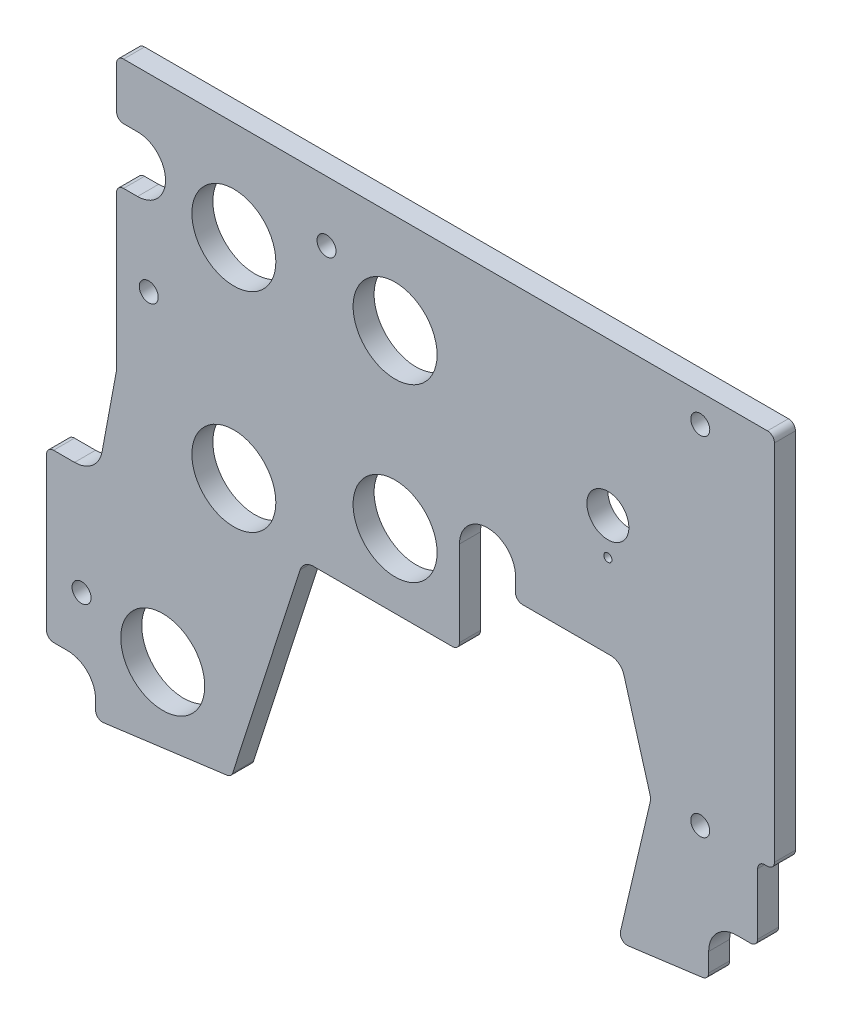
SolidWorks part; units mm, degrees
ref_plane "Front Plane" through (0, 0, 0) normal (0, 0, 1) x (1, 0, 0)
ref_plane "Top Plane" through (0, 0, 0) normal (0, 1, 0) x (1, 0, 0)
ref_plane "Right Plane" through (0, 0, 0) normal (1, 0, 0) x (0, 0, -1)
sketch "Sketch1" plane through (0, 0, 0) normal (0, 0, 1) x (1, 0, 0)
  line L24 (-1.5875, -85.5345) -> (-1.5875, -3.175)
  line L25 (-3.175, -1.5875) -> (-149.225, -1.5875)
  line L26 (-150.8125, -3.175) -> (-150.8125, -12.7)
  line L27 (-149.225, -14.2875) -> (-146.05, -14.2875)
  line L28 (-146.05, -26.9875) -> (-149.225, -26.9875)
  line L29 (-150.8125, -28.575) -> (-150.8125, -63.3539)
  line L30 (-150.8392, -63.6437) -> (-154.0942, -81.1696)
  line L31 (-160.3375, -86.36) -> (-165.1, -86.36)
  line L32 (-166.6875, -87.9475) -> (-166.6875, -122.5455)
  line L33 (-165.1, -124.133) -> (-161.925, -124.133)
  line L34 (-155.575, -130.483) -> (-155.575, -132.6404)
  line L35 (-153.7803, -134.2144) -> (-125.7711, -130.5269)
  line L36 (-124.467, -129.4389) -> (-109.1805, -81.8956)
  line L37 (-106.1579, -79.6925) -> (-74.6125, -79.6925)
  line L38 (-73.025, -78.105) -> (-73.025, -58.7375)
  line L39 (-60.325, -58.7375) -> (-60.325, -61.9125)
  line L40 (-58.7375, -63.5) -> (-38.7866, -63.5)
  line L41 (-35.7358, -65.7958) -> (-29.8313, -86.2841)
  line L42 (-29.7909, -87.8878) -> (-36.5223, -116.6102)
  line L43 (-34.7695, -118.5463) -> (-17.8903, -116.3241)
  line L44 (-16.51, -114.7502) -> (-16.51, -110.5169)
  line L45 (-10.16, -104.1528) -> (-6.985, -104.1528)
  line L46 (-5.3975, -102.5653) -> (-5.3975, -88.7095)
  line L47 (-3.81, -87.122) -> (-3.175, -87.122)
  line L48 (-1.5875, -85.5345) -> (-1.5875, -3.175)
  line L49 (-3.175, -1.5875) -> (-149.225, -1.5875)
  line L50 (-150.8125, -3.175) -> (-150.8125, -12.7)
  line L51 (-149.225, -14.2875) -> (-146.05, -14.2875)
  line L52 (-146.05, -26.9875) -> (-149.225, -26.9875)
  line L53 (-150.8125, -28.575) -> (-150.8125, -63.3539)
  line L54 (-150.8392, -63.6437) -> (-154.0942, -81.1696)
  line L55 (-160.3375, -86.36) -> (-165.1, -86.36)
  line L56 (-166.6875, -87.9475) -> (-166.6875, -122.5455)
  line L57 (-165.1, -124.133) -> (-161.925, -124.133)
  line L58 (-155.575, -130.483) -> (-155.575, -132.6404)
  line L59 (-153.7803, -134.2144) -> (-125.7711, -130.5269)
  line L60 (-124.467, -129.4389) -> (-109.1805, -81.8956)
  line L61 (-106.1579, -79.6925) -> (-74.6125, -79.6925)
  line L62 (-73.025, -78.105) -> (-73.025, -58.7375)
  line L63 (-60.325, -58.7375) -> (-60.325, -61.9125)
  line L64 (-58.7375, -63.5) -> (-38.7866, -63.5)
  line L65 (-35.7358, -65.7958) -> (-29.8313, -86.2841)
  line L66 (-29.7909, -87.8878) -> (-36.5223, -116.6102)
  line L67 (-34.7695, -118.5463) -> (-17.8903, -116.3241)
  line L68 (-16.51, -114.7502) -> (-16.51, -110.5169)
  line L69 (-10.16, -104.1528) -> (-6.985, -104.1528)
  line L70 (-5.3975, -102.5653) -> (-5.3975, -88.7095)
  line L71 (-3.81, -87.122) -> (-3.175, -87.122)
  arc A24 (-3.175, -87.122) -> (-1.5875, -85.5345) centre (-3.175, -85.5345) ccw
  arc A25 (-1.5875, -3.175) -> (-3.175, -1.5875) centre (-3.175, -3.175) ccw
  arc A26 (-149.225, -1.5875) -> (-150.8125, -3.175) centre (-149.225, -3.175) ccw
  arc A27 (-150.8125, -12.7) -> (-149.225, -14.2875) centre (-149.225, -12.7) ccw
  arc A28 (-146.05, -26.9875) -> (-146.05, -14.2875) centre (-146.05, -20.6375) ccw
  arc A29 (-149.225, -26.9875) -> (-150.8125, -28.575) centre (-149.225, -28.575) ccw
  arc A30 (-150.8392, -63.6437) -> (-150.8125, -63.3539) centre (-152.4, -63.3539) ccw
  arc A31 (-160.3375, -86.36) -> (-154.0942, -81.1696) centre (-160.3375, -80.01) ccw
  arc A32 (-165.1, -86.36) -> (-166.6875, -87.9475) centre (-165.1, -87.9475) ccw
  arc A33 (-166.6875, -122.5455) -> (-165.1, -124.133) centre (-165.1, -122.5455) ccw
  arc A34 (-155.575, -130.483) -> (-161.925, -124.133) centre (-161.925, -130.483) ccw
  arc A35 (-155.575, -132.6404) -> (-153.7803, -134.2144) centre (-153.9875, -132.6404) ccw
  arc A36 (-125.7711, -130.5269) -> (-124.467, -129.4389) centre (-125.9783, -128.953) ccw
  arc A37 (-106.1579, -79.6925) -> (-109.1805, -81.8956) centre (-106.1579, -82.8675) ccw
  arc A38 (-74.6125, -79.6925) -> (-73.025, -78.105) centre (-74.6125, -78.105) ccw
  arc A39 (-60.325, -58.7375) -> (-73.025, -58.7375) centre (-66.675, -58.7375) ccw
  arc A40 (-60.325, -61.9125) -> (-58.7375, -63.5) centre (-58.7375, -61.9125) ccw
  arc A41 (-35.7358, -65.7958) -> (-38.7866, -63.5) centre (-38.7866, -66.675) ccw
  arc A42 (-29.7909, -87.8878) -> (-29.8313, -86.2841) centre (-32.8822, -87.1633) ccw
  arc A43 (-36.5223, -116.6102) -> (-34.7695, -118.5463) centre (-34.9767, -116.9724) ccw
  arc A44 (-17.8903, -116.3241) -> (-16.51, -114.7502) centre (-18.0975, -114.7502) ccw
  arc A45 (-10.16, -104.1528) -> (-16.51, -110.5169) centre (-10.16, -110.5028) ccw
  arc A46 (-6.985, -104.1528) -> (-5.3975, -102.5653) centre (-6.985, -102.5653) ccw
  arc A47 (-3.81, -87.122) -> (-5.3975, -88.7095) centre (-3.81, -88.7095) ccw
  arc A48 (-3.175, -87.122) -> (-1.5875, -85.5345) centre (-3.175, -85.5345) ccw
  arc A49 (-1.5875, -3.175) -> (-3.175, -1.5875) centre (-3.175, -3.175) ccw
  arc A50 (-149.225, -1.5875) -> (-150.8125, -3.175) centre (-149.225, -3.175) ccw
  arc A51 (-150.8125, -12.7) -> (-149.225, -14.2875) centre (-149.225, -12.7) ccw
  arc A52 (-146.05, -26.9875) -> (-146.05, -14.2875) centre (-146.05, -20.6375) ccw
  arc A53 (-149.225, -26.9875) -> (-150.8125, -28.575) centre (-149.225, -28.575) ccw
  arc A54 (-150.8392, -63.6437) -> (-150.8125, -63.3539) centre (-152.4, -63.3539) ccw
  arc A55 (-160.3375, -86.36) -> (-154.0942, -81.1696) centre (-160.3375, -80.01) ccw
  arc A56 (-165.1, -86.36) -> (-166.6875, -87.9475) centre (-165.1, -87.9475) ccw
  arc A57 (-166.6875, -122.5455) -> (-165.1, -124.133) centre (-165.1, -122.5455) ccw
  arc A58 (-155.575, -130.483) -> (-161.925, -124.133) centre (-161.925, -130.483) ccw
  arc A59 (-155.575, -132.6404) -> (-153.7803, -134.2144) centre (-153.9875, -132.6404) ccw
  arc A60 (-125.7711, -130.5269) -> (-124.467, -129.4389) centre (-125.9783, -128.953) ccw
  arc A61 (-106.1579, -79.6925) -> (-109.1805, -81.8956) centre (-106.1579, -82.8675) ccw
  arc A62 (-74.6125, -79.6925) -> (-73.025, -78.105) centre (-74.6125, -78.105) ccw
  arc A63 (-60.325, -58.7375) -> (-73.025, -58.7375) centre (-66.675, -58.7375) ccw
  arc A64 (-60.325, -61.9125) -> (-58.7375, -63.5) centre (-58.7375, -61.9125) ccw
  arc A65 (-35.7358, -65.7958) -> (-38.7866, -63.5) centre (-38.7866, -66.675) ccw
  arc A66 (-29.7909, -87.8878) -> (-29.8313, -86.2841) centre (-32.8822, -87.1633) ccw
  arc A67 (-36.5223, -116.6102) -> (-34.7695, -118.5463) centre (-34.9767, -116.9724) ccw
  arc A68 (-17.8903, -116.3241) -> (-16.51, -114.7502) centre (-18.0975, -114.7502) ccw
  arc A69 (-10.16, -104.1528) -> (-16.51, -110.5169) centre (-10.16, -110.5028) ccw
  arc A70 (-6.985, -104.1528) -> (-5.3975, -102.5653) centre (-6.985, -102.5653) ccw
  arc A71 (-3.81, -87.122) -> (-5.3975, -88.7095) centre (-3.81, -88.7095) ccw
  dimension "D1" = 0
extrude "Boss-Extrude1" add sketch "Sketch1" along normal blind 4.7625
hole_wizard "#6 Clearance Hole1" positions "Sketch3" profile "Sketch2" hole size "#6" standard "ANSI Inch" end condition through all
sketch "Sketch3" plane through (0, 0, 4.7625) normal (0, 0, 1) x (1, 0, 0)
  point P0 (-103.1875, -15.24)
  point P3 (-18.415, -7.9375)
  point P6 (-143.51, -44.45)
  point P9 (-158.75, -111.125)
  point P12 (-18.415, -86.741)
sketch "Sketch2" plane through (-103.1875, -15.24, 4.7625) normal (1, 0, 0) x (0, -1, 0)
  line L0 (0, 0) -> (0, 4.7625)
  line L1 (0, 4.7625) -> (2.1526, 4.7625)
  line L2 (2.1526, 4.7625) -> (2.1526, 0)
  line L5 (2.1526, 0) -> (0, 0)
  line L11 (0, -6.35) -> (0, 107.95) construction
  dimension "Thru Hole Dia." = 4.3053
  dimension "Thru Hole Depth" = 4.7625
sketch "Sketch5" plane through (0, 0, 4.7625) normal (0, 0, 1) x (1, 0, 0)
  circle A0 centre (-124.206, -24.13) radius 9.525
  circle A1 centre (-87.63, -24.13) radius 9.525
  circle A2 centre (-87.63, -62.992) radius 9.525
  circle A3 centre (-124.206, -71.4375) radius 9.525
  circle A4 centre (-140.335, -115.57) radius 9.525
  circle A5 centre (-39.37, -36.322) radius 4.7625
  dimension "D1" = 19.05
  dimension "D2" = 9.525
extrude "Cut-Extrude1" cut sketch "Sketch5" against normal through all
hole_wizard "#0 Clearance Hole1" positions "Sketch6" profile "Sketch7" hole size "#0" standard "ANSI Inch" end condition through all
sketch "Sketch6" plane through (0, 0, 6.35) normal (0, 0, 1) x (1, 0, 0)
  point P0 (-39.37, -44.577)
sketch "Sketch7" plane through (-39.37, -44.577, 6.35) normal (1, 0, 0) x (0, -1, 0)
  line L0 (0, 0) -> (0, 6.35)
  line L1 (0, 6.35) -> (0.9271, 6.35)
  line L2 (0.9271, 6.35) -> (0.9271, 0)
  line L3 (0.9271, 0) -> (0, 0)
  line L4 (0, -6.35) -> (0, 107.95) construction
  dimension "Thru Hole Dia." = 1.8542
  dimension "Thru Hole Depth" = 6.35
